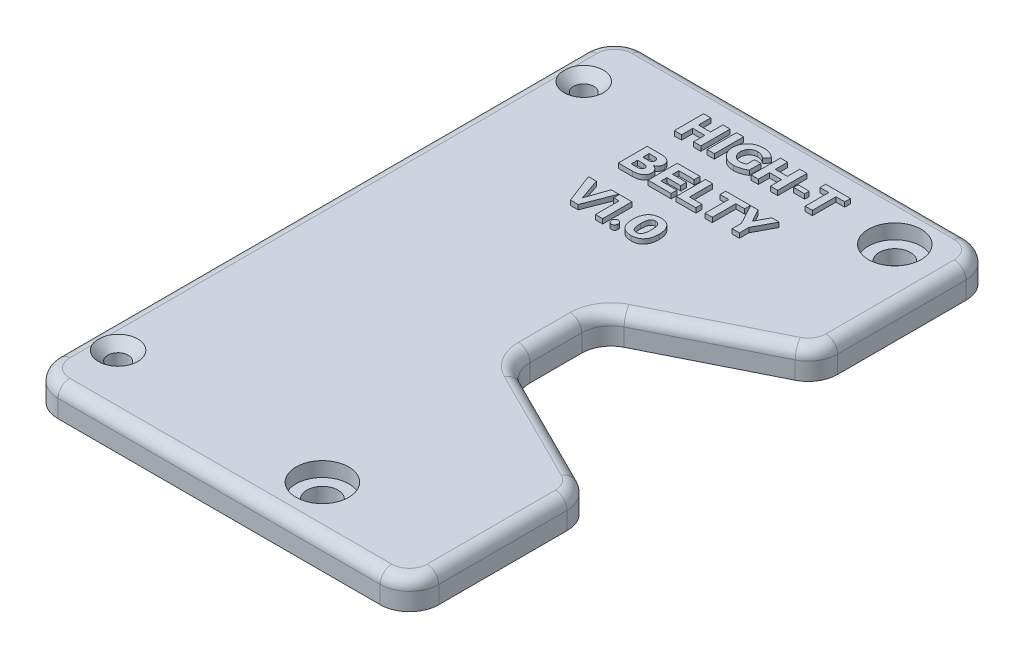
SolidWorks part; units mm, degrees
ref_plane "Front Plane" through (0, 0, 0) normal (0, 0, 1) x (1, 0, 0)
ref_plane "Top Plane" through (0, 0, 0) normal (0, 1, 0) x (1, 0, 0)
ref_plane "Right Plane" through (0, 0, 0) normal (1, 0, 0) x (0, 0, -1)
sketch "Sketch2" plane through (0, 0, 0) normal (0, 1, 0) x (1, 0, 0)
  line L1 (-32.5, 50) -> (32.5, 50)
  line L2 (-32.5, 50) -> (-32.5, -50)
  line L3 (-32.5, -50) -> (32.5, -50)
  line L4 (32.5, 50) -> (32.5, -50)
  line L5 (-32.5, 50) -> (32.5, -50) construction
  line L6 (-32.5, -50) -> (32.5, 50) construction
  circle A0 centre (-27.5, 39.75) radius 1.75
  circle A1 centre (-27.5, -39.75) radius 1.75
  circle A2 centre (23.15, 42.205) radius 2.65
  circle A3 centre (9.4375, -41.8075) radius 2.65
  circle A4 centre (23.15, 42.205) radius 3.5 construction
  circle A6 centre (9.4375, -41.8075) radius 2.5 construction
  point P0 (0, 0)
  dimension "D3" = 3.5
  dimension "D4" = 5
  dimension "D8" = 5.3
  dimension "D1" = 65
  dimension "D2" = 100
  dimension "D5" = 5
  dimension "D6" = 10.25
  dimension "D7" = 10.25
extrude "Boss-Extrude1" add sketch "Sketch2" along normal blind 5
sketch "Sketch3" plane through (0, 5, 0) normal (0, 1, 0) x (1, 0, 0)
  circle A0 centre (23.15, 42.205) radius 4.5
  circle A1 centre (9.4375, -41.8075) radius 4.5
  dimension "D1" = 9
  dimension "D2" = 9
extrude "Cut-Extrude1" cut sketch "Sketch3" against normal blind 2.5
fillet "Fillet1" radius 5 4 edges at (-32.5, 2.5, 50) (-32.5, 2.5, -50) (32.5, 2.5, -50) (32.5, 2.5, 50)
chamfer "Chamfer1" distance 1.6 angle 45 2 edges at (-27.5, 5, 41.5) (-27.5, 5, -38)
sketch "Sketch6" plane through (0, 5, 0) normal (0, 1, 0) x (1, 0, 0)
  line L0 (7.5, 7.5) -> (32.5, 20)
  line L1 (32.5, -45) -> (32.5, 45) construction
  line L2 (32.5, 20) -> (32.5, -20)
  line L3 (32.5, -20) -> (7.5, -7.5)
  line L4 (7.5, -7.5) -> (7.5, 7.5)
  point P4 (7.5, 0)
  dimension "D1" = 25
  dimension "D2" = 40
  dimension "D3" = 15
extrude "Cut-Extrude2" cut sketch "Sketch6" against normal through all
fillet "Fillet3" radius 5 4 edges at (32.5, 2.5, -20) (7.5, 2.5, -7.5) (7.5, 2.5, 7.5) (32.5, 2.5, 20)
fillet "Fillet2" radius 2 16 edges at (-31.0355, 5, 48.5355) (-32.5, 5, 0) (-31.0355, 5, -48.5355) (0, 5, -50) (31.0355, 5, -48.5355) (32.5, 5, -34.0451) (32.5, 5, 34.0451) (31.0355, 5, 48.5355) (0, 5, 50) (31.7533, 5, -20.4615) (20, 5, -13.75) (8.2467, 5, -7.0385) (7.5, 5, 0) (8.2467, 5, 7.0385) (20, 5, 13.75) (31.7533, 5, 20.4615)
sketch "Sketch4" plane through (0, 5, 0) normal (0, 1, 0) x (1, 0, 0)
  text T0 "<b>HIGH-T</b>\r\n<b>BELTY</b>\r\n<b>V1.0</b>" font "Montserrat" height 5
extrude "Boss-Extrude2" add sketch "Sketch4" along normal blind 0.8
